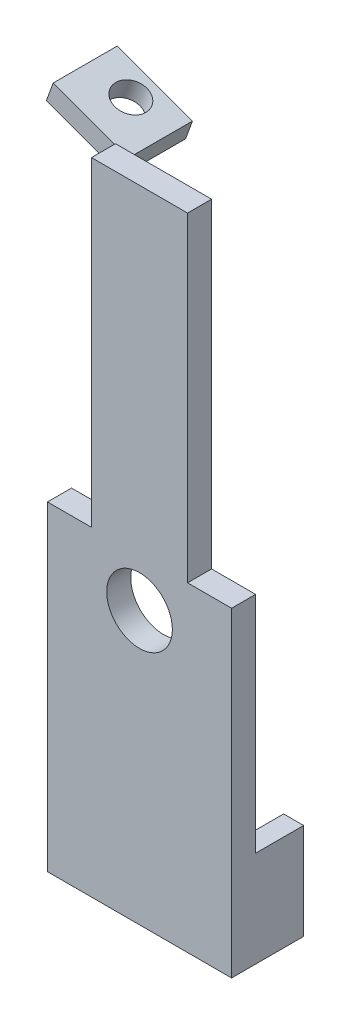
SolidWorks part; units mm, degrees
ref_plane "Front Plane" through (0, 0, 0) normal (0, 0, 1) x (1, 0, 0)
ref_plane "Top Plane" through (0, 0, 0) normal (0, 1, 0) x (1, 0, 0)
ref_plane "Right Plane" through (0, 0, 0) normal (1, 0, 0) x (0, 0, -1)
sketch "Sketch1" plane through (0, 0, 0) normal (0, 0, 1) x (1, 0, 0)
  line L1 (-11.5, 0) -> (11.5, 0)
  line L2 (-11.5, 0) -> (-11.5, 40)
  line L3 (-11.5, 40) -> (11.5, 40)
  line L4 (11.5, 0) -> (11.5, 40)
  point P4 (0, 0)
  dimension "D1" = 23
  dimension "D2" = 40
extrude "Boss-Extrude1" add sketch "Sketch1" against normal blind 3
sketch "Sketch2" plane through (0, 0, 0) normal (0, 0, 1) x (1, 0, 0)
  line L0 (11.5, 40) -> (-11.5, 40) construction
  circle A0 centre (0, 34) radius 4.1
  point P2 (0, 0)
  dimension "D2" = 8.2
  dimension "D1" = 6
extrude "Cut-Extrude1" cut sketch "Sketch2" against normal blind 3
sketch "Sketch3" plane through (0, 40, 0) normal (0, 1, 0) x (1, 0, 0)
  line L0 (11.5, 3) -> (-11.5, 3) construction
  line L1 (-6, 3) -> (6, 3)
  line L2 (-6, 3) -> (-6, 0)
  line L3 (-6, 0) -> (6, 0)
  line L4 (6, 3) -> (6, 0)
  line L5 (11.5, 0) -> (-11.5, 0) construction
  point P8 (0, 3)
  dimension "D1" = 12
extrude "Boss-Extrude2" add sketch "Sketch3" along normal blind 40
sketch "Sketch4" plane through (0, 0, -3) normal (0, 0, -1) x (-1, 0, 0)
  line L1 (-11.5, 0) -> (-9, 0)
  line L2 (-11.5, 0) -> (-11.5, 12)
  line L3 (-11.5, 12) -> (-9, 12)
  line L4 (-9, 0) -> (-9, 12)
  dimension "D1" = 12
  dimension "D2" = 2.5
extrude "Boss-Extrude3" add sketch "Sketch4" along normal blind 6
sketch "Sketch5" plane through (0, 0, -3) normal (0, 0, -1) x (-1, 0, 0)
  point P0 (0, 75)
  point P1 (0, 0)
  point P3 (0, 0)
  point P4 (0, 0)
  point P5 (0, 0)
  dimension "D1" = 75
ref_point "Point1"
ref_axis "Axis1" through (0, 75, -3) along (0, 0, -1)
ref_plane "Plane1" through (24.1045, 66.2267, 0) normal (0.342, 0.9397, 0) x (0, 0, -1)
sketch "Sketch6" plane through (24.1045, 66.2267, 0) normal (0.342, 0.9397, 0) x (0, 0, -1)
  line L1 (11, 31.229) -> (3, 31.229)
  line L2 (11, 31.229) -> (11, 41.229)
  line L3 (11, 41.229) -> (3, 41.229)
  line L4 (3, 31.229) -> (3, 41.229)
  line L6 (3, -4.353) -> (3, -6.7022) construction
  dimension "D1" = 8
  dimension "D2" = 10
extrude "Boss-Extrude4" add sketch "Sketch6" along normal blind 2.5
sketch "Sketch7" plane through (24.1045, 66.2267, 0) normal (-0.342, -0.9397, 0) x (0.9397, -0.342, 0)
  line L1 (-32.0366, -3) -> (-31.229, -3) construction
  line L2 (-41.229, -11) -> (-41.229, -3) construction
  circle A0 centre (-36.229, -8) radius 2
  dimension "D3" = 4
  dimension "D1" = 5
  dimension "D2" = 5
extrude "Cut-Extrude2" cut sketch "Sketch7" against normal through all
